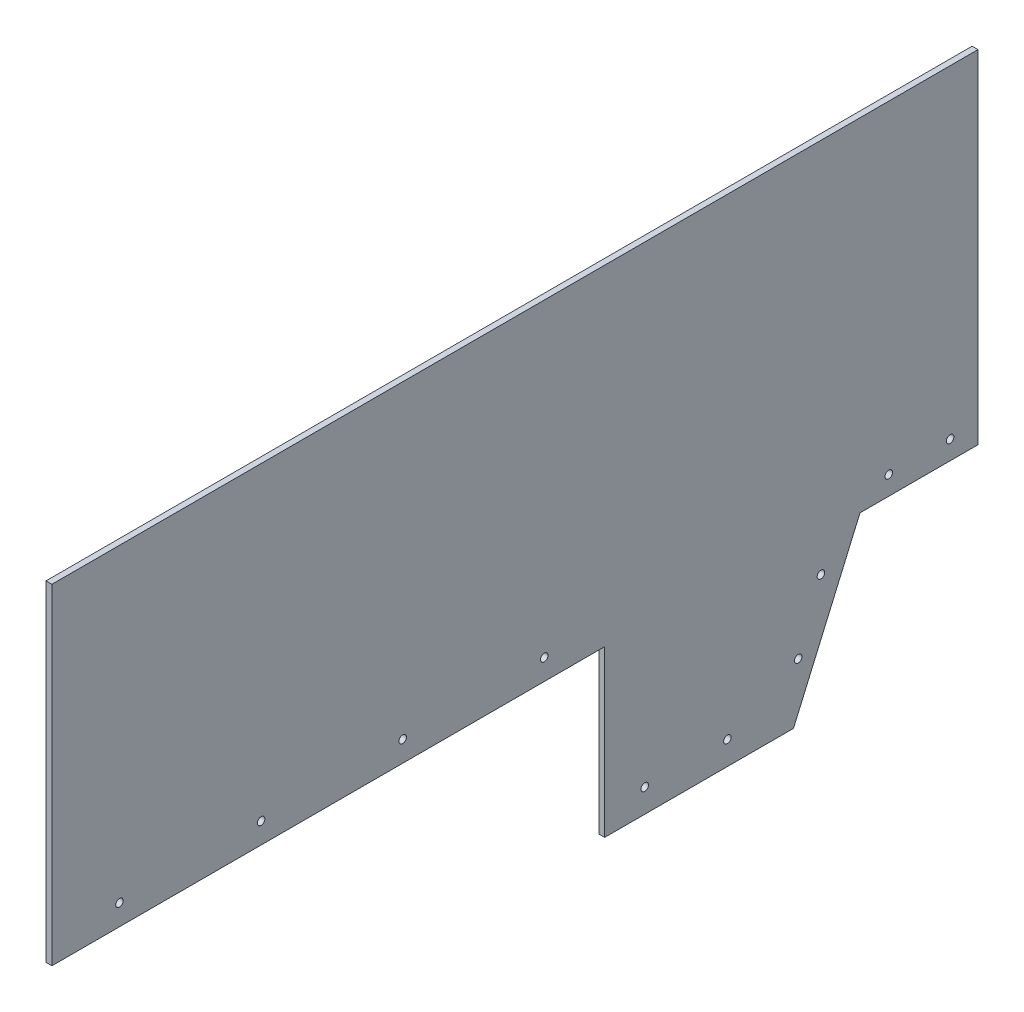
SolidWorks part; units mm, degrees
material "6061-T6 (SS)"
ref_plane "X-Y Datum" through (0, 0, 0) normal (0, 0, 1) x (1, 0, 0)
ref_plane "X-Z Datum" through (0, 0, 0) normal (0, 1, 0) x (1, 0, 0)
ref_plane "Y-Z Datum" through (0, 0, 0) normal (1, 0, 0) x (0, 0, -1)
sketch "Sketch1" plane through (0, 0, 0) normal (1, 0, 0) x (0, 0, -1)
  line L1 (-249.174, 88.9) -> (249.174, 88.9)
  line L2 (-249.174, 88.9) -> (-249.174, -88.9)
  line L3 (-249.174, -88.9) -> (249.174, -88.9)
  line L4 (249.174, 88.9) -> (249.174, -88.9)
  line L5 (-249.174, 88.9) -> (249.174, -88.9) construction
  line L6 (-249.174, -88.9) -> (249.174, 88.9) construction
  point P0 (0, 0)
  dimension "D1" = 177.8
  dimension "D2" = 498.348
extrude "Boss-Extrude1" add sketch "Sketch1" along normal mid plane 3.175
sketch "Sketch2" plane through (1.5875, 0, 0) normal (1, 0, 0) x (0, 0, -1)
  line L0 (249.174, -88.9) -> (249.174, -95.25)
  line L1 (249.174, -95.25) -> (185.674, -95.25)
  line L2 (185.674, -95.25) -> (149.8854, -177.8)
  line L3 (149.8854, -177.8) -> (48.2854, -177.8)
  line L4 (48.2854, -177.8) -> (48.2854, -88.9)
  line L5 (-249.174, -88.9) -> (249.174, -88.9) construction
  line L6 (48.2854, -88.9) -> (249.174, -88.9)
  line L8 (48.2854, -76.2) -> (48.2854, 88.9)
  line L10 (249.174, -88.9) -> (249.174, 88.9) construction
  line M10 (-249.174, -88.9) -> (249.174, -88.9)
  dimension "D1" = 6.35
  dimension "D2" = 63.5
  dimension "D3" = 88.9
  dimension "D4" = 101.6
extrude "Boss-Extrude2" add sketch "Sketch2" against normal blind 3.175 contours L4 L3 L2 L1 L0 M10 region at (1.5875, -129.6106, -113.0883)
sketch "Sketch3" plane through (1.5875, 0, 0) normal (1, 0, 0) x (0, 0, -1)
  line L2 (48.2854, -77.7064) -> (15.7854, -77.7064)
  line L5 (48.2854, -88.9) -> (48.2854, -66.5127)
  circle A1 centre (15.7854, -77.7064) radius 2.025
extrude "Cut-Extrude1" cut sketch "Sketch3" against normal through all contours A1 region at (1.5875, -77.7064, -13.8177)
pattern_linear "LPattern1" count 4 spacing 76.2 along (0, 0, 1) of "Cut-Extrude1"
sketch "Sketch4" plane through (-1.5875, 0, 0) normal (-1, 0, 0) x (0, 0, 1)
  line L0 (-69.8754, -177.8) -> (-69.8754, -165.1)
  line L2 (-149.8854, -177.8) -> (-48.2854, -177.8) construction
  line L3 (-48.2854, -165.1) -> (-69.8754, -165.1)
  line L4 (-48.2854, -177.8) -> (-48.2854, -88.9) construction
  circle A0 centre (-69.8754, -165.1) radius 2.025
extrude "Cut-Extrude2" cut sketch "Sketch4" against normal through all contours L3 A0 L0 | L0 A0 L3 region at (-1.5875, -164.8135, -70.1619) region at (-1.5875, -165.9594, -69.016)
pattern_linear "LPattern2" count 2 spacing 44.45 along (0, 0, -1) of "Cut-Extrude2"
sketch "Sketch5" plane through (-1.5875, 0, 0) normal (-1, 0, 0) x (0, 0, 1)
  line L0 (-161.6752, -150.6055) -> (-152.4002, -146.5844)
  line L1 (-185.674, -95.25) -> (-149.8854, -177.8) construction
  circle A0 centre (-152.4002, -146.5844) radius 2.025
extrude "Cut-Extrude3" cut sketch "Sketch5" against normal through all contours A0 region at (-1.5875, -148.5111, -152.0005)
sketch "Sketch8" plane through (-1.5875, 0, 0) normal (-1, 0, 0) x (0, 0, 1)
  line L0 (-152.4002, -146.5844) -> (-166.5117, -114.2867)
  line L1 (-166.5117, -114.2867) -> (-164.6496, -113.4732)
  circle A0 centre (-164.6496, -113.4732) radius 2.025
extrude "Cut-Extrude5" cut sketch "Sketch8" against normal through all contours A0 region at (-1.5875, -115.3993, -164.2472)
sketch "Sketch9" plane through (-1.5875, 0, 0) normal (-1, 0, 0) x (0, 0, 1)
  line L0 (-201.1707, -95.25) -> (-201.1707, -85.09)
  line L1 (-249.174, -95.25) -> (-185.674, -95.25) construction
  circle A0 centre (-201.1707, -85.09) radius 2.025
extrude "Cut-Extrude6" cut sketch "Sketch9" against normal through all contours A0 region at (-1.5875, -86.4814, -199.7793)
pattern_linear "LPattern4" count 2 spacing 33.02 along (0, 0, -1) of "Cut-Extrude6"
